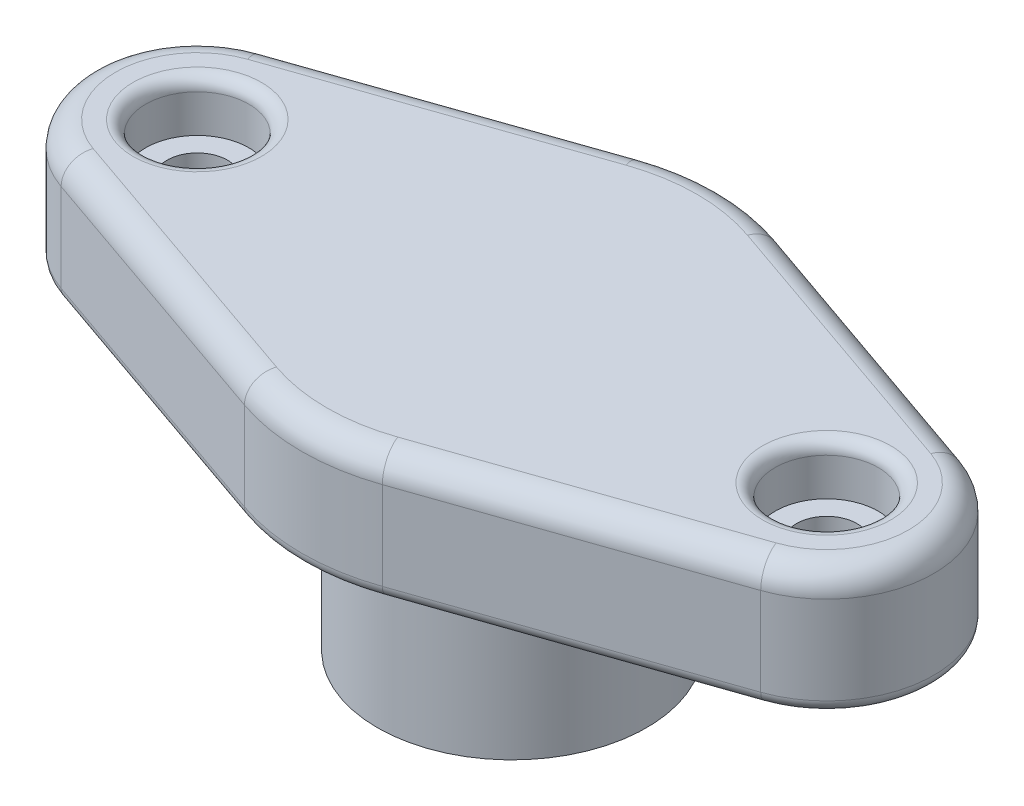
SolidWorks part; units mm, degrees
ref_plane "Front Plane" through (0, 0, 0) normal (0, 0, 1) x (1, 0, 0)
ref_plane "Top Plane" through (0, 0, 0) normal (0, 1, 0) x (1, 0, 0)
ref_plane "Right Plane" through (0, 0, 0) normal (1, 0, 0) x (0, 0, -1)
sketch "Sketch1" plane through (0, 0, 0) normal (0, 1, 0) x (1, 0, 0)
  circle A0 centre (0, 0) radius 5.35
  point P3 (0, 0)
  dimension "D1" = 10.7
extrude "Boss-Extrude1" add sketch "Sketch1" along normal blind 7
sketch "Sketch2" plane through (0, 7, 0) normal (0, 1, 0) x (1, 0, 0)
  line L0 (-12.5, 0) -> (12.5, 0) construction
  line L1 (2.7388, 7.8881) -> (13.894, 4.0149)
  line L2 (-2.7388, -7.8881) -> (-13.894, -4.0149)
  line L3 (13.894, -4.0149) -> (2.7388, -7.8881)
  line L7 (-13.894, 4.0149) -> (-2.7388, 7.8881)
  arc A0 (-2.7388, -7.8881) -> (2.7388, -7.8881) centre (0, 0) ccw
  circle A2 centre (12.5, 0) radius 1.2
  circle A3 centre (-12.5, 0) radius 1.2
  arc A4 (13.894, -4.0149) -> (13.894, 4.0149) centre (12.5, 0) ccw
  arc A7 (2.7388, 7.8881) -> (-2.7388, 7.8881) centre (0, 0) ccw
  arc A9 (-13.894, 4.0149) -> (-13.894, -4.0149) centre (-12.5, 0) ccw
  point P5 (0, 0)
  point P10 (-1.4687, -8.2198)
  point P16 (-24.5806, 0.3044)
  point P19 (3.8795, 10.186)
  dimension "D1" = 16.7
  dimension "D2" = 2.4
  dimension "D3" = 2.4
  dimension "D5" = 8.35
  dimension "D6" = 8.5
  dimension "D7" = 4.25
  dimension "D4" = 25
extrude "Boss-Extrude2" add sketch "Sketch2" along normal blind 5
sketch "Sketch3" plane through (0, 12, 0) normal (0, 1, 0) x (1, 0, 0)
  circle A0 centre (-12.5, 0) radius 2.05
  circle A1 centre (12.5, 0) radius 2.05
  dimension "D1" = 4.1
  dimension "D2" = 4.1
extrude "Cut-Extrude1" cut sketch "Sketch3" against normal blind 2
fillet "Fillet1" radius 0.5 10 edges at (12.5, 12, 2.05) (-12.5, 12, 2.05) (-16.75, 7, 0) (-8.3164, 7, -5.9515) (0, 7, -8.35) (8.3164, 7, -5.9515) (16.75, 7, 0) (8.3164, 7, 5.9515) (0, 7, 8.35) (-8.3164, 7, 5.9515)
fillet "Fillet2" radius 1 8 edges at (-8.3164, 12, -5.9515) (0, 12, -8.35) (8.3164, 12, -5.9515) (16.75, 12, 0) (8.3164, 12, 5.9515) (0, 12, 8.35) (-8.3164, 12, 5.9515) (-16.75, 12, 0)
sketch "Sketch4" plane through (0, 0, 0) normal (0, -1, 0) x (1, 0, 0)
  circle A0 centre (0, 0) radius 3.5
  dimension "D1" = 7
extrude "Cut-Extrude2" cut sketch "Sketch4" against normal blind 2
fillet "Fillet3" radius 1 2 edges at (0, 0, -3.5) (0, 2, -3.5)
